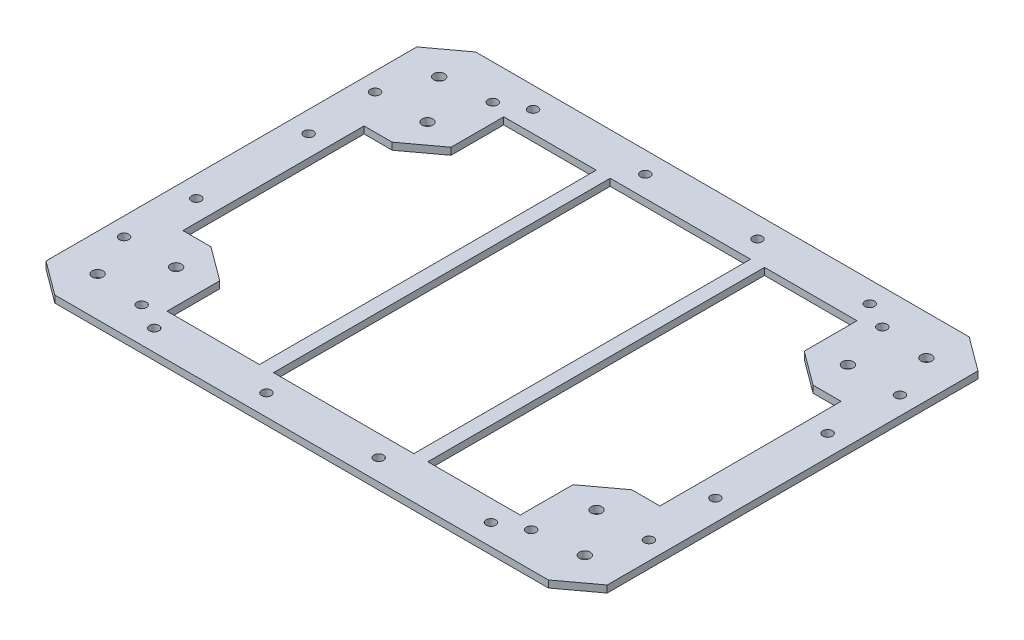
SolidWorks part; units mm, degrees
material "Thornel Mat VMA"
ref_plane "Front Plane" through (0, 0, 0) normal (0, 0, 1) x (1, 0, 0)
ref_plane "Top Plane" through (0, 0, 0) normal (0, 1, 0) x (1, 0, 0)
ref_plane "Right Plane" through (0, 0, 0) normal (1, 0, 0) x (0, 0, -1)
sketch "Sketch1" plane through (0, 0, 0) normal (0, 1, 0) x (1, 0, 0)
  line L0 (-127, 83.9186) -> (-111.6865, 95.25)
  line L1 (-127, -95.25) -> (127, -95.25)
  line L2 (-127, -95.25) -> (-127, 95.25)
  line L3 (-127, 95.25) -> (127, 95.25)
  line L4 (127, -95.25) -> (127, 95.25)
  line L5 (-107.95, 41.011) -> (-107.95, -41.011)
  line L7 (-38.1, -76.2) -> (-38.1, 76.2)
  line L8 (-107.95, 41.011) -> (-95.25, 41.011)
  line L9 (-31.75, -76.2) -> (-31.75, 76.2)
  line L10 (-127, 95.25) -> (127, -95.25) construction
  line L12 (127, 83.9186) -> (111.6865, 95.25)
  line L13 (38.1, -76.2) -> (38.1, 76.2)
  line L14 (79.9365, 52.3423) -> (79.9365, 76.2)
  line L15 (95.25, 41.011) -> (79.9365, 52.3423)
  line L16 (107.95, 41.011) -> (95.25, 41.011)
  line L17 (107.95, 41.011) -> (107.95, -41.011)
  line L18 (127, -83.9186) -> (111.6865, -95.25)
  line L19 (107.95, -41.011) -> (95.25, -41.011)
  line L20 (95.25, -41.011) -> (79.9365, -52.3423)
  line L21 (79.9365, -52.3423) -> (79.9365, -76.2)
  line L22 (127, 0) -> (-127, 0) construction
  line L23 (0, -13.6985) -> (0, 95.25) construction
  line L25 (-79.9365, -76.2) -> (-38.1, -76.2)
  line L26 (-79.9365, -52.3423) -> (-79.9365, -76.2)
  line L27 (-95.25, 41.011) -> (-127, 83.9186) construction
  line L28 (-95.25, 41.011) -> (-79.9365, 52.3423)
  line L29 (-79.9365, 52.3423) -> (-79.9365, 76.2)
  line L30 (-79.9365, 76.2) -> (-38.1, 76.2)
  line L31 (-95.25, -41.011) -> (-79.9365, -52.3423)
  line L32 (-107.95, -41.011) -> (-95.25, -41.011)
  line L33 (-127, -83.9186) -> (-111.6865, -95.25)
  line L34 (-79.9365, 52.3423) -> (-111.6865, 95.25) construction
  line L35 (31.75, -76.2) -> (31.75, 76.2)
  line L36 (-31.75, 76.2) -> (31.75, 76.2)
  line L37 (38.1, 76.2) -> (79.9365, 76.2)
  line L38 (-31.75, -76.2) -> (31.75, -76.2)
  line L39 (38.1, -76.2) -> (79.9365, -76.2)
  point P0 (0, 0)
  point P1 (0, 0)
  point P14 (0, 0)
  point P22 (0, 76.2)
  point P33 (107.95, 0)
  point P41 (0, 0)
  point P44 (-107.95, 0)
  point P45 (-38.1, 0)
  point P46 (-31.75, 0)
  dimension "D1" = 190.5
  dimension "D2" = 254
  dimension "D3" = 19.05
  dimension "D4" = 19.05
  dimension "D9" = 31.75
  dimension "D5" = 143.5
  dimension "D6" = 19.05
  dimension "D7" = 12.7
  dimension "D8" = 6.35
extrude "Boss-Extrude1" add sketch "Sketch1" along normal blind 3.175 contours L2 L1 L4 L3 L8 region at (-117.4547, 0, -87.0321)
sketch "Sketch2" plane through (0, 3.175, 0) normal (0, 1, 0) x (1, 0, 0)
  line L0 (-87.5933, 46.6767) -> (-119.3433, 89.5843) construction
  line L1 (-95.25, 41.011) -> (-79.9365, 52.3423) construction
  line L2 (-127, 83.9186) -> (-111.6865, 95.25) construction
  line L3 (0, 0) -> (0, 95.25) construction
  line L4 (-111.6865, 95.25) -> (111.6865, 95.25) construction
  line L5 (0, 0) -> (-127, 0) construction
  line L6 (-127, -83.9186) -> (-127, 83.9186) construction
  line L7 (-103.4683, 68.1305) -> (-88.1548, 79.4619) construction
  circle A0 centre (-95.1475, 56.8856) radius 2.4638
  circle A1 centre (-110.256, 77.3036) radius 2.4638
  circle A2 centre (110.256, 77.3036) radius 2.4638
  circle A3 centre (95.1475, 56.8856) radius 2.4638
  circle A4 centre (110.256, -77.3036) radius 2.4638
  circle A5 centre (95.1475, -56.8856) radius 2.4638
  circle A6 centre (-110.256, -77.3036) radius 2.4638
  circle A7 centre (-95.1475, -56.8856) radius 2.4638
  circle A8 centre (-88.1548, 79.4619) radius 2.159
  circle A9 centre (-118.7817, 56.7991) radius 2.159
  circle A10 centre (118.7817, 56.7991) radius 2.159
  circle A11 centre (88.1548, 79.4619) radius 2.159
  circle A12 centre (118.7817, -56.7991) radius 2.159
  circle A13 centre (88.1548, -79.4619) radius 2.159
  circle A14 centre (-88.1548, -79.4619) radius 2.159
  circle A15 centre (-118.7817, -56.7991) radius 2.159
  dimension "D2" = 4.9276
  dimension "D3" = 4.9276
  dimension "D5" = 4.318
  dimension "D1" = 25.4
  dimension "D4" = 12.7
  dimension "D6" = 19.05
extrude "Cut-Extrude1" cut sketch "Sketch2" against normal through all
sketch "Sketch3" plane through (0, 3.175, 0) normal (0, 1, 0) x (1, 0, 0)
  line L0 (-79.9365, 76.2) -> (-79.9365, 95.25) construction
  line L1 (-111.6865, 95.25) -> (111.6865, 95.25) construction
  line L2 (-79.9365, 85.725) -> (79.9365, 85.725) construction
  line L3 (79.9365, 76.2) -> (79.9365, 95.25) construction
  line L4 (0, 0) -> (76.2, 0) construction
  line L5 (-107.95, -41.011) -> (-127, -41.011) construction
  line L6 (-127, -83.9186) -> (-127, 83.9186) construction
  line L7 (-107.95, 41.011) -> (-127, 41.011) construction
  line L8 (-117.475, 41.011) -> (-117.475, -41.011) construction
  line L9 (0, 0) -> (0, 36.2879) construction
  circle A0 centre (-76.2, 85.725) radius 2.159
  circle A1 centre (-25.4, 85.725) radius 2.159
  circle A2 centre (25.4, 85.725) radius 2.159
  circle A3 centre (76.2, 85.725) radius 2.159
  circle A4 centre (76.2, -85.725) radius 2.159
  circle A5 centre (25.4, -85.725) radius 2.159
  circle A6 centre (-25.4, -85.725) radius 2.159
  circle A7 centre (-76.2, -85.725) radius 2.159
  circle A8 centre (-117.475, -25.4) radius 2.159
  circle A9 centre (-117.475, 25.4) radius 2.159
  circle A10 centre (117.475, 25.4) radius 2.159
  circle A11 centre (117.475, -25.4) radius 2.159
  point P12 (0, 85.725)
  point P40 (-117.475, 0)
  dimension "D1" = 4.318
  dimension "D2" = 76.2
  dimension "D4" = 4.318
  dimension "D5" = 25.4
  dimension "D3" = 4
  dimension "D6" = 2
extrude "Cut-Extrude2" cut sketch "Sketch3" against normal through all
sketch "Sketch4" plane through (0, 3.175, 0) normal (0, 1, 0) x (1, 0, 0)
  line L0 (-95.1475, -56.8856) -> (-110.256, -74.8398) construction
